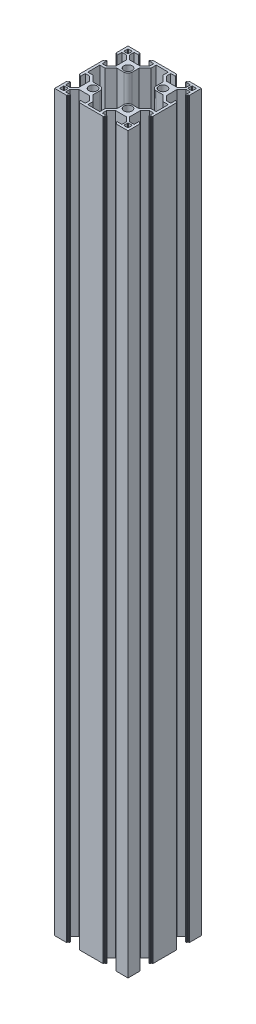
SolidWorks part; units mm, degrees
ref_plane "Front Plane" through (0, 0, 0) normal (0, 0, 1) x (1, 0, 0)
ref_plane "Top Plane" through (0, 0, 0) normal (0, 1, 0) x (1, 0, 0)
ref_plane "Right Plane" through (0, 0, 0) normal (1, 0, 0) x (0, 0, -1)
sketch "Sketch1" plane through (0, 0, 0) normal (0, 1, 0) x (1, 0, 0)
  line L0 (0, 30) -> (0, -30) construction
  line L1 (-30, -30) -> (30, -30)
  line L2 (-30, -30) -> (-30, 30)
  line L3 (-30, 30) -> (30, 30)
  line L4 (30, -30) -> (30, 30)
  line L5 (-30, -30) -> (30, 30) construction
  line L6 (-30, 30) -> (30, -30) construction
  line L7 (-30, 0) -> (30, 0) construction
  line L8 (-23.05, -28) -> (-6.95, -28)
  line L9 (-6.95, -28) -> (-6.95, -24.4)
  line L10 (-6.95, -24.4) -> (-10.615, -20.8)
  line L11 (-10.615, -20.8) -> (-19.385, -20.8)
  line L12 (-19.385, -20.8) -> (-23.05, -24.4)
  line L13 (-23.05, -24.4) -> (-23.05, -28)
  line L14 (10.615, -20.8) -> (19.385, -20.8)
  line L15 (6.95, -24.4) -> (10.615, -20.8)
  line L16 (6.95, -28) -> (6.95, -24.4)
  line L17 (23.05, -28) -> (6.95, -28)
  line L18 (23.05, -24.4) -> (23.05, -28)
  line L19 (19.385, -20.8) -> (23.05, -24.4)
  line L20 (19.385, 20.8) -> (23.05, 24.4)
  line L21 (23.05, 24.4) -> (23.05, 28)
  line L22 (23.05, 28) -> (6.95, 28)
  line L23 (6.95, 28) -> (6.95, 24.4)
  line L24 (6.95, 24.4) -> (10.615, 20.8)
  line L25 (10.615, 20.8) -> (19.385, 20.8)
  line L26 (-23.05, 24.4) -> (-23.05, 28)
  line L27 (-19.385, 20.8) -> (-23.05, 24.4)
  line L28 (-10.615, 20.8) -> (-19.385, 20.8)
  line L29 (-6.95, 24.4) -> (-10.615, 20.8)
  line L30 (-6.95, 28) -> (-6.95, 24.4)
  line L31 (-23.05, 28) -> (-6.95, 28)
  line L32 (-20.8, 19.385) -> (-24.4, 23.05)
  line L33 (-24.4, 23.05) -> (-28, 23.05)
  line L34 (-28, 23.05) -> (-28, 6.95)
  line L35 (-28, 6.95) -> (-24.4, 6.95)
  line L36 (-24.4, 6.95) -> (-20.8, 10.615)
  line L37 (-20.8, 10.615) -> (-20.8, 19.385)
  line L38 (-24.4, -23.05) -> (-28, -23.05)
  line L39 (-20.8, -19.385) -> (-24.4, -23.05)
  line L40 (-20.8, -10.615) -> (-20.8, -19.385)
  line L41 (-24.4, -6.95) -> (-20.8, -10.615)
  line L42 (-28, -6.95) -> (-24.4, -6.95)
  line L43 (-28, -23.05) -> (-28, -6.95)
  line L44 (20.8, -19.385) -> (24.4, -23.05)
  line L45 (24.4, -23.05) -> (28, -23.05)
  line L46 (28, -23.05) -> (28, -6.95)
  line L47 (28, -6.95) -> (24.4, -6.95)
  line L48 (24.4, -6.95) -> (20.8, -10.615)
  line L49 (20.8, -10.615) -> (20.8, -19.385)
  line L50 (24.4, 23.05) -> (28, 23.05)
  line L51 (20.8, 19.385) -> (24.4, 23.05)
  line L52 (20.8, 10.615) -> (20.8, 19.385)
  line L53 (24.4, 6.95) -> (20.8, 10.615)
  line L54 (28, 6.95) -> (24.4, 6.95)
  line L55 (28, 23.05) -> (28, 6.95)
  point P0 (0, 0)
  dimension "D1" = 60
  dimension "D2" = 16.1
  dimension "D3" = 8.77
  dimension "D4" = 3.6
  dimension "D5" = 7.2
  dimension "D6" = 2
  dimension "D7" = 6.95
extrude "Boss-Extrude1" add sketch "Sketch1" along normal blind 600
sketch "Sketch2" plane through (0, 600, 0) normal (0, 1, 0) x (1, 0, 0)
  line L0 (-19.1, -28) -> (-19.1, -29)
  line L1 (-23.05, -28) -> (-6.95, -28) construction
  line L2 (-30, -30) -> (30, -30) construction
  line L3 (-10.9, -28) -> (-10.9, -29)
  line L4 (-10.9, -29) -> (-9.9, -29)
  line L5 (-9.9, -29) -> (-9.9, -30)
  line L6 (-19.1, -29) -> (-20.1, -29)
  line L7 (-20.1, -29) -> (-20.1, -30)
  line L8 (-19.1, -28) -> (-10.9, -28)
  line L9 (-20.1, -30) -> (-9.9, -30)
  dimension "D1" = 8.2
  dimension "D2" = 3.95
  dimension "D3" = 1
  dimension "D4" = 1
extrude "Cut-Extrude1" cut sketch "Sketch2" against normal through all
mirror "Mirror1" about plane through (0, 0, 0) normal (1, 0, 0) of "Cut-Extrude1"
ref_axis "Axis1" through (0, 1050, 0) along (0, -1, 0)
pattern_circular "CirPattern1" count 4 over 360 about axis through (0, 1050, 0) along (0, -1, 0) of "Cut-Extrude1", "Mirror1"
sketch "Sketch4" plane through (0, 600, 0) normal (0, 1, 0) x (1, 0, 0)
  line L0 (19.385, 18.8) -> (9.797, 18.8) construction
  line L1 (-18.8, 18.8) -> (-18.8, 9.797)
  line L2 (18.8, -19.385) -> (18.8, -9.797) construction
  line L3 (28, 4.95) -> (28, -4.95)
  line L4 (-18.8, -9.797) -> (-18.8, -19.385) construction
  line L5 (4.95, -28) -> (-4.95, -28)
  line L6 (-9.797, 18.8) -> (-9.797, 13.197)
  line L7 (-28, -4.95) -> (-28, 4.95)
  line L8 (-18.8, 9.797) -> (-23.5611, 4.95)
  line L9 (-23.5611, 4.95) -> (-28, 4.95)
  line L10 (18.8, 18.8) -> (9.797, 18.8)
  line L11 (9.797, 18.8) -> (4.95, 23.5611)
  line L12 (4.95, 23.5611) -> (4.95, 28)
  line L13 (4.95, 28) -> (4.95, 28)
  line L14 (4.95, 28) -> (4.95, 28)
  line L15 (4.95, 28) -> (4.95, 28)
  line L16 (4.95, 28) -> (4.95, 28)
  line L17 (4.95, 28) -> (-4.95, 28)
  line L18 (-4.95, 28) -> (-4.95, 28)
  line L19 (-4.95, 28) -> (-4.95, 28)
  line L20 (-4.95, 28) -> (-4.95, 28)
  line L21 (-4.95, 28) -> (-4.95, 28)
  line L22 (-4.95, 28) -> (-4.95, 23.5611)
  line L23 (-4.95, 23.5611) -> (-9.797, 18.8)
  line L24 (-9.797, 18.8) -> (-18.8, 18.8)
  line L25 (28, 4.95) -> (23.5611, 4.95)
  line L26 (23.5611, 4.95) -> (18.8, 9.797)
  line L27 (18.8, 9.797) -> (18.8, 18.8)
  line L28 (18.8, -18.8) -> (18.8, -9.797)
  line L29 (18.8, -9.797) -> (23.5611, -4.95)
  line L30 (23.5611, -4.95) -> (28, -4.95)
  line L31 (4.95, -28) -> (4.95, -23.5611)
  line L32 (4.95, -23.5611) -> (9.797, -18.8)
  line L33 (9.797, -18.8) -> (18.8, -18.8)
  line L34 (-18.8, -18.8) -> (-9.797, -18.8)
  line L35 (-9.797, -18.8) -> (-4.95, -23.5611)
  line L36 (-4.95, -23.5611) -> (-4.95, -28)
  line L37 (-28, -4.95) -> (-23.5611, -4.95)
  line L38 (-23.5611, -4.95) -> (-18.8, -9.797)
  line L39 (-18.8, -9.797) -> (-18.8, -18.8)
  line L40 (-9.797, 18.8) -> (-19.385, 18.8) construction
  line L41 (-18.8, 19.385) -> (-18.8, 9.797) construction
  line L42 (18.8, 9.797) -> (18.8, 19.385) construction
  line L43 (9.797, -18.8) -> (19.385, -18.8) construction
  line L44 (-19.385, -18.8) -> (-9.797, -18.8) construction
  line L45 (-13.197, 9.797) -> (-18.8, 9.797)
  line L46 (9.797, 18.8) -> (9.797, 13.197)
  line L47 (13.197, 9.797) -> (18.8, 9.797)
  line L48 (-18.8, -9.797) -> (-13.197, -9.797)
  line L49 (-9.797, -13.197) -> (-9.797, -18.8)
  line L50 (9.797, -18.8) -> (9.797, -13.197)
  line L51 (13.197, -9.797) -> (18.8, -9.797)
  line L52 (-27.5, -28) -> (-24.9, -28)
  line L53 (24.9, -28) -> (27.5, -28)
  line L54 (24.4, -27.5) -> (24.4, -24.9)
  line L55 (24.9, -24.4) -> (27.5, -24.4)
  line L56 (28, -27.5) -> (28, -24.9)
  line L57 (24.4, -28) -> (28, -24.4) construction
  line L58 (24.4, -24.4) -> (28, -28) construction
  line L59 (-28, -24.9) -> (-28, -27.5)
  line L60 (-27.5, -24.4) -> (-24.9, -24.4)
  line L61 (-24.4, -24.9) -> (-24.4, -27.5)
  line L62 (-28, 27.5) -> (-28, 24.9)
  line L63 (-24.9, 28) -> (-27.5, 28)
  line L64 (-24.4, 27.5) -> (-24.4, 24.9)
  line L65 (-24.9, 24.4) -> (-27.5, 24.4)
  line L66 (27.5, 28) -> (24.9, 28)
  line L67 (28, 24.9) -> (28, 27.5)
  line L68 (27.5, 24.4) -> (24.9, 24.4)
  line L69 (24.4, 24.9) -> (24.4, 27.5)
  line L116 (28, 19.1) -> (29, 19.1)
  line L117 (29, 19.1) -> (29, 20.1)
  line L118 (29, 20.1) -> (30, 20.1)
  line L119 (30, 20.1) -> (30, 30)
  line L120 (30, 30) -> (20.1, 30)
  line L121 (20.1, 30) -> (20.1, 29)
  line L122 (20.1, 29) -> (19.1, 29)
  line L123 (19.1, 29) -> (19.1, 28)
  line L124 (19.1, 28) -> (23.05, 28)
  line L125 (23.05, 28) -> (23.05, 24.4)
  line L126 (23.05, 24.4) -> (19.385, 20.8)
  line L127 (19.385, 20.8) -> (10.615, 20.8)
  line L128 (10.615, 20.8) -> (6.95, 24.4)
  line L129 (6.95, 24.4) -> (6.95, 28)
  line L130 (6.95, 28) -> (10.9, 28)
  line L131 (10.9, 28) -> (10.9, 29)
  line L132 (10.9, 29) -> (9.9, 29)
  line L133 (9.9, 29) -> (9.9, 30)
  line L134 (9.9, 30) -> (-9.9, 30)
  line L135 (-9.9, 30) -> (-9.9, 29)
  line L136 (-9.9, 29) -> (-10.9, 29)
  line L137 (-10.9, 29) -> (-10.9, 28)
  line L138 (-10.9, 28) -> (-6.95, 28)
  line L139 (-6.95, 28) -> (-6.95, 24.4)
  line L140 (-6.95, 24.4) -> (-10.615, 20.8)
  line L141 (-10.615, 20.8) -> (-19.385, 20.8)
  line L142 (-19.385, 20.8) -> (-23.05, 24.4)
  line L143 (-23.05, 24.4) -> (-23.05, 28)
  line L144 (-23.05, 28) -> (-19.1, 28)
  line L145 (-19.1, 28) -> (-19.1, 29)
  line L146 (-19.1, 29) -> (-20.1, 29)
  line L147 (-20.1, 29) -> (-20.1, 30)
  line L148 (-20.1, 30) -> (-30, 30)
  line L149 (-30, 30) -> (-30, 20.1)
  line L150 (-30, 20.1) -> (-29, 20.1)
  line L151 (-29, 20.1) -> (-29, 19.1)
  line L152 (-29, 19.1) -> (-28, 19.1)
  line L153 (-28, 19.1) -> (-28, 23.05)
  line L154 (-28, 23.05) -> (-24.4, 23.05)
  line L155 (-24.4, 23.05) -> (-20.8, 19.385)
  line L156 (-20.8, 19.385) -> (-20.8, 10.615)
  line L157 (-20.8, 10.615) -> (-24.4, 6.95)
  line L158 (-24.4, 6.95) -> (-28, 6.95)
  line L159 (-28, 6.95) -> (-28, 10.9)
  line L160 (-28, 10.9) -> (-29, 10.9)
  line L161 (-29, 10.9) -> (-29, 9.9)
  line L162 (-29, 9.9) -> (-30, 9.9)
  line L163 (-30, 9.9) -> (-30, -9.9)
  line L164 (-30, -9.9) -> (-29, -9.9)
  line L165 (-29, -9.9) -> (-29, -10.9)
  line L166 (-29, -10.9) -> (-28, -10.9)
  line L167 (-28, -10.9) -> (-28, -6.95)
  line L168 (-28, -6.95) -> (-24.4, -6.95)
  line L169 (-24.4, -6.95) -> (-20.8, -10.615)
  line L170 (-20.8, -10.615) -> (-20.8, -19.385)
  line L171 (-20.8, -19.385) -> (-24.4, -23.05)
  line L172 (-24.4, -23.05) -> (-28, -23.05)
  line L173 (-28, -23.05) -> (-28, -19.1)
  line L174 (-28, -19.1) -> (-29, -19.1)
  line L175 (-29, -19.1) -> (-29, -20.1)
  line L176 (-29, -20.1) -> (-30, -20.1)
  line L177 (-30, -20.1) -> (-30, -30)
  line L178 (-30, -30) -> (-20.1, -30)
  line L179 (-20.1, -30) -> (-20.1, -29)
  line L180 (-20.1, -29) -> (-19.1, -29)
  line L181 (-19.1, -29) -> (-19.1, -28)
  line L182 (-19.1, -28) -> (-23.05, -28)
  line L183 (-23.05, -28) -> (-23.05, -24.4)
  line L184 (-23.05, -24.4) -> (-19.385, -20.8)
  line L185 (-19.385, -20.8) -> (-10.615, -20.8)
  line L186 (-10.615, -20.8) -> (-6.95, -24.4)
  line L187 (-6.95, -24.4) -> (-6.95, -28)
  line L188 (-6.95, -28) -> (-10.9, -28)
  line L189 (-10.9, -28) -> (-10.9, -29)
  line L190 (-10.9, -29) -> (-9.9, -29)
  line L191 (-9.9, -29) -> (-9.9, -30)
  line L192 (-9.9, -30) -> (9.9, -30)
  line L193 (9.9, -30) -> (9.9, -29)
  line L194 (9.9, -29) -> (10.9, -29)
  line L195 (10.9, -29) -> (10.9, -28)
  line L196 (10.9, -28) -> (6.95, -28)
  line L197 (6.95, -28) -> (6.95, -24.4)
  line L198 (6.95, -24.4) -> (10.615, -20.8)
  line L199 (10.615, -20.8) -> (19.385, -20.8)
  line L200 (19.385, -20.8) -> (23.05, -24.4)
  line L201 (23.05, -24.4) -> (23.05, -28)
  line L202 (23.05, -28) -> (19.1, -28)
  line L203 (19.1, -28) -> (19.1, -29)
  line L204 (19.1, -29) -> (20.1, -29)
  line L205 (20.1, -29) -> (20.1, -30)
  line L206 (20.1, -30) -> (30, -30)
  line L207 (30, -30) -> (30, -20.1)
  line L208 (30, -20.1) -> (29, -20.1)
  line L209 (29, -20.1) -> (29, -19.1)
  line L210 (29, -19.1) -> (28, -19.1)
  line L211 (28, -19.1) -> (28, -23.05)
  line L212 (28, -23.05) -> (24.4, -23.05)
  line L213 (24.4, -23.05) -> (20.8, -19.385)
  line L214 (20.8, -19.385) -> (20.8, -10.615)
  line L215 (20.8, -10.615) -> (24.4, -6.95)
  line L216 (24.4, -6.95) -> (28, -6.95)
  line L217 (28, -6.95) -> (28, -10.9)
  line L218 (28, -10.9) -> (29, -10.9)
  line L219 (29, -10.9) -> (29, -9.9)
  line L220 (29, -9.9) -> (30, -9.9)
  line L221 (30, -9.9) -> (30, 9.9)
  line L222 (30, 9.9) -> (29, 9.9)
  line L223 (29, 9.9) -> (29, 10.9)
  line L224 (29, 10.9) -> (28, 10.9)
  line L225 (28, 10.9) -> (28, 6.95)
  line L226 (28, 6.95) -> (24.4, 6.95)
  line L227 (24.4, 6.95) -> (20.8, 10.615)
  line L228 (20.8, 10.615) -> (20.8, 19.385)
  line L229 (20.8, 19.385) -> (24.4, 23.05)
  line L230 (24.4, 23.05) -> (28, 23.05)
  line L231 (28, 23.05) -> (28, 19.1)
  line L232 (28, 19.1) -> (29, 19.1)
  line L233 (29, 19.1) -> (29, 20.1)
  line L234 (29, 20.1) -> (30, 20.1)
  line L235 (30, 20.1) -> (30, 30)
  line L236 (30, 30) -> (20.1, 30)
  line L237 (20.1, 30) -> (20.1, 29)
  line L238 (20.1, 29) -> (19.1, 29)
  line L239 (19.1, 29) -> (19.1, 28)
  line L240 (19.1, 28) -> (23.05, 28)
  line L241 (23.05, 28) -> (23.05, 24.4)
  line L242 (23.05, 24.4) -> (19.385, 20.8)
  line L243 (19.385, 20.8) -> (10.615, 20.8)
  line L244 (10.615, 20.8) -> (6.95, 24.4)
  line L245 (6.95, 24.4) -> (6.95, 28)
  line L246 (6.95, 28) -> (10.9, 28)
  line L247 (10.9, 28) -> (10.9, 29)
  line L248 (10.9, 29) -> (9.9, 29)
  line L249 (9.9, 29) -> (9.9, 30)
  line L250 (9.9, 30) -> (-9.9, 30)
  line L251 (-9.9, 30) -> (-9.9, 29)
  line L252 (-9.9, 29) -> (-10.9, 29)
  line L253 (-10.9, 29) -> (-10.9, 28)
  line L254 (-10.9, 28) -> (-6.95, 28)
  line L255 (-6.95, 28) -> (-6.95, 24.4)
  line L256 (-6.95, 24.4) -> (-10.615, 20.8)
  line L257 (-10.615, 20.8) -> (-19.385, 20.8)
  line L258 (-19.385, 20.8) -> (-23.05, 24.4)
  line L259 (-23.05, 24.4) -> (-23.05, 28)
  line L260 (-23.05, 28) -> (-19.1, 28)
  line L261 (-19.1, 28) -> (-19.1, 29)
  line L262 (-19.1, 29) -> (-20.1, 29)
  line L263 (-20.1, 29) -> (-20.1, 30)
  line L264 (-20.1, 30) -> (-30, 30)
  line L265 (-30, 30) -> (-30, 20.1)
  line L266 (-30, 20.1) -> (-29, 20.1)
  line L267 (-29, 20.1) -> (-29, 19.1)
  line L268 (-29, 19.1) -> (-28, 19.1)
  line L269 (-28, 19.1) -> (-28, 23.05)
  line L270 (-28, 23.05) -> (-24.4, 23.05)
  line L271 (-24.4, 23.05) -> (-20.8, 19.385)
  line L272 (-20.8, 19.385) -> (-20.8, 10.615)
  line L273 (-20.8, 10.615) -> (-24.4, 6.95)
  line L274 (-24.4, 6.95) -> (-28, 6.95)
  line L275 (-28, 6.95) -> (-28, 10.9)
  line L276 (-28, 10.9) -> (-29, 10.9)
  line L277 (-29, 10.9) -> (-29, 9.9)
  line L278 (-29, 9.9) -> (-30, 9.9)
  line L279 (-30, 9.9) -> (-30, -9.9)
  line L280 (-30, -9.9) -> (-29, -9.9)
  line L281 (-29, -9.9) -> (-29, -10.9)
  line L282 (-29, -10.9) -> (-28, -10.9)
  line L283 (-28, -10.9) -> (-28, -6.95)
  line L284 (-28, -6.95) -> (-24.4, -6.95)
  line L285 (-24.4, -6.95) -> (-20.8, -10.615)
  line L286 (-20.8, -10.615) -> (-20.8, -19.385)
  line L287 (-20.8, -19.385) -> (-24.4, -23.05)
  line L288 (-24.4, -23.05) -> (-28, -23.05)
  line L289 (-28, -23.05) -> (-28, -19.1)
  line L290 (-28, -19.1) -> (-29, -19.1)
  line L291 (-29, -19.1) -> (-29, -20.1)
  line L292 (-29, -20.1) -> (-30, -20.1)
  line L293 (-30, -20.1) -> (-30, -30)
  line L294 (-30, -30) -> (-20.1, -30)
  line L295 (-20.1, -30) -> (-20.1, -29)
  line L296 (-20.1, -29) -> (-19.1, -29)
  line L297 (-19.1, -29) -> (-19.1, -28)
  line L298 (-19.1, -28) -> (-23.05, -28)
  line L299 (-23.05, -28) -> (-23.05, -24.4)
  line L300 (-23.05, -24.4) -> (-19.385, -20.8)
  line L301 (-19.385, -20.8) -> (-10.615, -20.8)
  line L302 (-10.615, -20.8) -> (-6.95, -24.4)
  line L303 (-6.95, -24.4) -> (-6.95, -28)
  line L304 (-6.95, -28) -> (-10.9, -28)
  line L305 (-10.9, -28) -> (-10.9, -29)
  line L306 (-10.9, -29) -> (-9.9, -29)
  line L307 (-9.9, -29) -> (-9.9, -30)
  line L308 (-9.9, -30) -> (9.9, -30)
  line L309 (9.9, -30) -> (9.9, -29)
  line L310 (9.9, -29) -> (10.9, -29)
  line L311 (10.9, -29) -> (10.9, -28)
  line L312 (10.9, -28) -> (6.95, -28)
  line L313 (6.95, -28) -> (6.95, -24.4)
  line L314 (6.95, -24.4) -> (10.615, -20.8)
  line L315 (10.615, -20.8) -> (19.385, -20.8)
  line L316 (19.385, -20.8) -> (23.05, -24.4)
  line L317 (23.05, -24.4) -> (23.05, -28)
  line L318 (23.05, -28) -> (19.1, -28)
  line L319 (19.1, -28) -> (19.1, -29)
  line L320 (19.1, -29) -> (20.1, -29)
  line L321 (20.1, -29) -> (20.1, -30)
  line L322 (20.1, -30) -> (30, -30)
  line L323 (30, -30) -> (30, -20.1)
  line L324 (30, -20.1) -> (29, -20.1)
  line L325 (29, -20.1) -> (29, -19.1)
  line L326 (29, -19.1) -> (28, -19.1)
  line L327 (28, -19.1) -> (28, -23.05)
  line L328 (28, -23.05) -> (24.4, -23.05)
  line L329 (24.4, -23.05) -> (20.8, -19.385)
  line L330 (20.8, -19.385) -> (20.8, -10.615)
  line L331 (20.8, -10.615) -> (24.4, -6.95)
  line L332 (24.4, -6.95) -> (28, -6.95)
  line L333 (28, -6.95) -> (28, -10.9)
  line L334 (28, -10.9) -> (29, -10.9)
  line L335 (29, -10.9) -> (29, -9.9)
  line L336 (29, -9.9) -> (30, -9.9)
  line L337 (30, -9.9) -> (30, 9.9)
  line L338 (30, 9.9) -> (29, 9.9)
  line L339 (29, 9.9) -> (29, 10.9)
  line L340 (29, 10.9) -> (28, 10.9)
  line L341 (28, 10.9) -> (28, 6.95)
  line L342 (28, 6.95) -> (24.4, 6.95)
  line L343 (24.4, 6.95) -> (20.8, 10.615)
  line L344 (20.8, 10.615) -> (20.8, 19.385)
  line L345 (20.8, 19.385) -> (24.4, 23.05)
  line L346 (24.4, 23.05) -> (28, 23.05)
  line L347 (28, 23.05) -> (28, 19.1)
  circle A0 centre (14.2985, 14.2985) radius 3.4
  arc A1 (13.197, -9.797) -> (9.797, -13.197) centre (13.197, -13.197) ccw
  arc A2 (-9.797, -13.197) -> (-13.197, -9.797) centre (-13.197, -13.197) ccw
  arc A3 (13.197, 9.797) -> (9.797, 13.197) centre (13.197, 13.197) cw
  arc A4 (-9.797, 13.197) -> (-13.197, 9.797) centre (-13.197, 13.197) cw
  circle A5 centre (14.2985, -14.2985) radius 3.4
  circle A6 centre (-14.2985, -14.2985) radius 3.4
  circle A7 centre (-14.2985, 14.2985) radius 3.4
  arc A8 (24.4, -27.5) -> (24.9, -28) centre (24.9, -27.5) ccw
  arc A9 (28, -27.5) -> (27.5, -28) centre (27.5, -27.5) cw
  arc A10 (28, -24.9) -> (27.5, -24.4) centre (27.5, -24.9) ccw
  arc A11 (24.4, -24.9) -> (24.9, -24.4) centre (24.9, -24.9) cw
  arc A12 (-27.5, -28) -> (-28, -27.5) centre (-27.5, -27.5) cw
  arc A13 (-27.5, -24.4) -> (-28, -24.9) centre (-27.5, -24.9) ccw
  arc A14 (-24.9, -24.4) -> (-24.4, -24.9) centre (-24.9, -24.9) cw
  arc A15 (-24.9, -28) -> (-24.4, -27.5) centre (-24.9, -27.5) ccw
  arc A16 (-28, 27.5) -> (-27.5, 28) centre (-27.5, 27.5) cw
  arc A17 (-24.4, 27.5) -> (-24.9, 28) centre (-24.9, 27.5) ccw
  arc A18 (-24.4, 24.9) -> (-24.9, 24.4) centre (-24.9, 24.9) cw
  arc A19 (-28, 24.9) -> (-27.5, 24.4) centre (-27.5, 24.9) ccw
  arc A20 (27.5, 28) -> (28, 27.5) centre (27.5, 27.5) cw
  arc A21 (27.5, 24.4) -> (28, 24.9) centre (27.5, 24.9) ccw
  arc A22 (24.9, 24.4) -> (24.4, 24.9) centre (24.9, 24.9) cw
  arc A23 (24.9, 28) -> (24.4, 27.5) centre (24.9, 27.5) ccw
  point P102 (26.2, -26.2)
  point P104 (14.2985, 18.8)
  point P106 (18.8, 14.2985)
  point P140 (0, 0)
  point P239 (0, 0)
  dimension "D3" = 6.8
  dimension "D4" = 3.4
  dimension "D6" = 0.5
  dimension "D1" = 0
  dimension "D2" = 2
  dimension "D5" = 4
  dimension "D7" = 4
extrude "Cut-Extrude2" cut sketch "Sketch4" against normal through all contours L6 A4 L45 L8 L9 L7 L37 L38 L48 A2 L49 L35 L36 L5 L31 L32 L50 A1 L51 L29 L30 L3 L25 L26 L47 A3 L46 L11 L12 L17 L22 L23 | A7 | A0 | L66 A23 L69 A22 L68 A21 L67 A20 | L62 A19 L65 A18 L64 A17 L63 A16 | L52 A15 L61 A14 L60 A13 L59 A12 | A11 L54 A8 L53 A9 L56 A10 L55 | A6 | A5 region at (0, 600, 0) region at (-26.2, 600, 26.2) region at (26.2, 600, 26.2) region at (-26.2, 600, -26.2) region at (26.2, 600, -26.2) region at (14.2985, 600, -14.2985) region at (-14.2985, 600, -14.2985)
fillet "Fillet1" radius 0.2 16 edges at (28, 300, -19.1) (30, 300, -20.1) (29, 300, -20.1) (29, 300, -19.1) (28, 300, 10.9) (29, 300, 9.9) (28, 300, 19.1) (29, 300, 20.1) (30, 300, 20.1) (29, 300, 19.1) (29, 300, 10.9) (30, 300, 9.9) (30, 300, -9.9) (29, 300, -9.9) (29, 300, -10.9) (28, 300, -10.9)
fillet "Fillet2" radius 0.2 20 edges at (-20.1, 0, -29.5) (-20.1, 600, -29.5) (-20.1, 300, -29) (-19.6, 0, -29) (-19.1, 300, -29) (-19.6, 600, -29) (-9.9, 300, -30) (-10.9, 300, -28) (-10.9, 300, -29) (-9.9, 300, -29) (19.1, 300, -28) (19.1, 300, -29) (20.1, 300, -29) (20.1, 300, -30) (10.9, 300, -28) (10.9, 300, -29) (9.9, 300, -29) (9.9, 300, -30) (-19.1, 300, -28) (-20.1, 300, -30)
fillet "Fillet3" radius 0.2 14 edges at (-29, 300, 9.9) (-29, 300, -20.1) (-30, 300, -20.1) (-29, 300, -19.1) (-28, 300, -10.9) (-29, 300, -10.9) (-29, 300, -9.9) (-30, 300, -9.9) (-29, 300, 10.9) (-30, 300, 9.9) (-28, 300, 19.1) (-29, 300, 19.1) (-29, 300, 20.1) (-30, 300, 20.1)
fillet "Fillet4" radius 0.2 16 edges at (-19.1, 300, 28) (10.9, 300, 28) (19.1, 300, 28) (20.1, 300, 29) (-10.9, 300, 28) (-9.9, 300, 29) (9.9, 300, 29) (-20.1, 300, 29) (19.1, 300, 29) (20.1, 300, 30) (10.9, 300, 29) (9.9, 300, 30) (-9.9, 300, 30) (-10.9, 300, 29) (-19.1, 300, 29) (-20.1, 300, 30)
